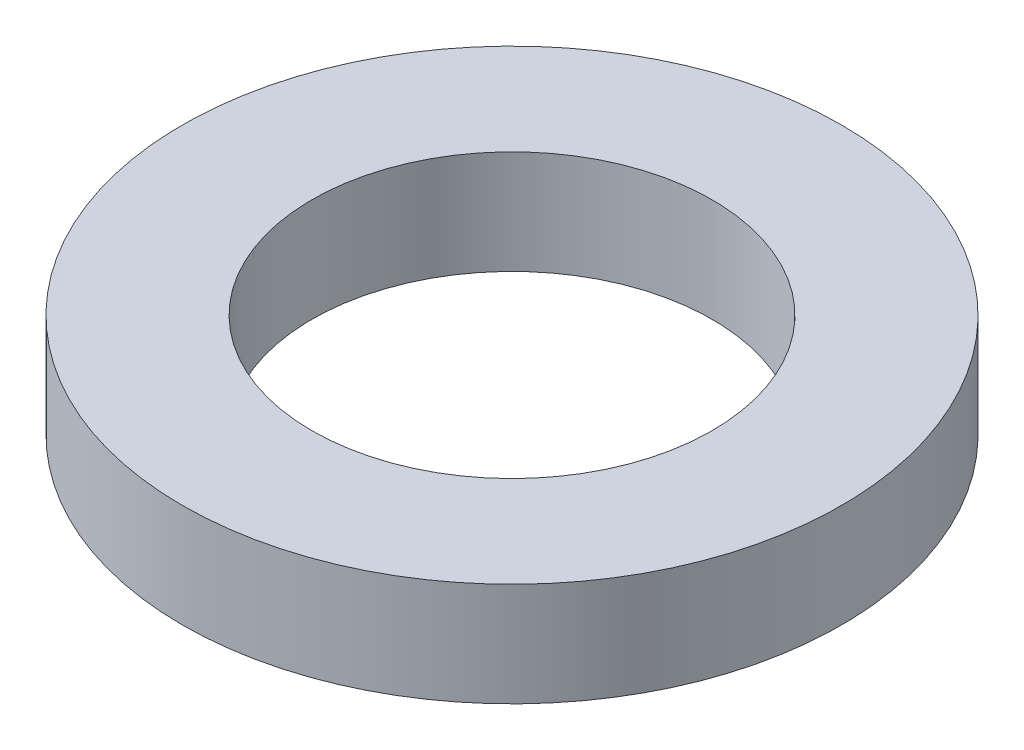
SolidWorks part; units mm, degrees
ref_plane "Front Plane" through (0, 0, 0) normal (0, 0, 1) x (1, 0, 0)
ref_plane "Top Plane" through (0, 0, 0) normal (0, 1, 0) x (1, 0, 0)
ref_plane "Right Plane" through (0, 0, 0) normal (1, 0, 0) x (0, 0, -1)
sketch "Sketch1" plane through (0, 0, 0) normal (0, 1, 0) x (1, 0, 0)
  circle A0 centre (0, 0) radius 70
  dimension "FLANGE_OD" = 140
extrude "Boss-Extrude1" add sketch "Sketch1" along normal blind 22
sketch "Sketch2" plane through (0, 0, 0) normal (0, 1, 0) x (1, 0, 0)
  circle A0 centre (0, 0) radius 42.5
  dimension "BORE_D" = 85
extrude "Cut-Extrude1" cut sketch "Sketch2" along normal through all
sketch "Sketch3" plane through (0, 22, 0) normal (0, 1, 0) x (1, 0, 0)
  circle A0 centre (0, 0) radius 27.0624 construction
  circle A1 centre (-27.0624, 0) radius 4.7562
  dimension "BOLT_D" = 9.5124
  dimension "BOLT_PCD" = 54.1247
extrude "Cut-Extrude2" cut sketch "Sketch3" against normal blind 17.7329 rebuild error yes
pattern_circular "CirPattern1" count 3 over 360 rebuild error yes
